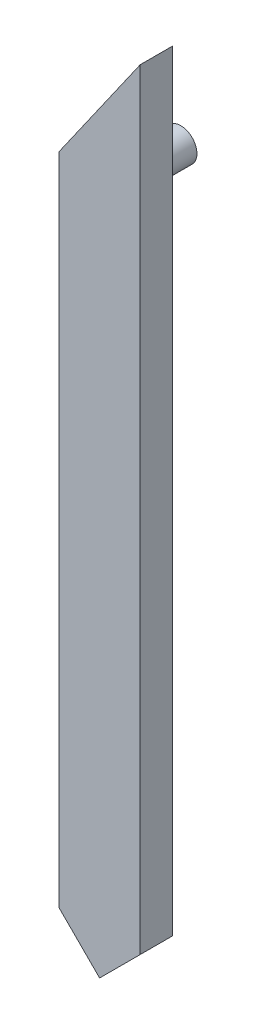
SolidWorks part; units mm, degrees
ref_plane "Front Plane" through (0, 0, 0) normal (0, 0, 1) x (1, 0, 0)
ref_plane "Top Plane" through (0, 0, 0) normal (0, 1, 0) x (1, 0, 0)
ref_plane "Right Plane" through (0, 0, 0) normal (1, 0, 0) x (0, 0, -1)
sketch "Sketch1" plane through (0, 0, 0) normal (0, 0, 1) x (1, 0, 0)
  line L1 (-5, 50) -> (5, 50)
  line L2 (-5, 50) -> (-5, -50)
  line L3 (-5, -50) -> (5, -50)
  line L4 (5, 50) -> (5, -50)
  line L5 (-5, 50) -> (5, -50) construction
  line L6 (-5, -50) -> (5, 50) construction
  point P0 (0, 0)
  dimension "D1" = 100
  dimension "D2" = 10
extrude "Boss-Extrude1" add sketch "Sketch1" along normal blind 4
sketch "Sketch2" plane through (0, 0, 4) normal (0, 0, 1) x (1, 0, 0)
  line L0 (5, 50) -> (-5, 35.7185)
  line L1 (-5, 50) -> (-5, -50) construction
  line L2 (-5, 35.7185) -> (-5, 50)
  line L3 (-5, 50) -> (5, 50)
  dimension "D1" = 145
extrude "Cut-Extrude1" cut sketch "Sketch2" against normal blind 4
chamfer "Chamfer1" distance 5 angle 45 2 edges at (-5, -50, 2) (5, -50, 2)
sketch "Sketch3" plane through (0, 0, 4) normal (0, 0, 1) x (1, 0, 0)
  line L0 (5, -45) -> (5, 50) construction
  circle A0 centre (0, 34) radius 2
  point P6 (5, 50)
  dimension "D1" = 4
  dimension "D2" = 5
  dimension "D3" = 16
extrude "Boss-Extrude2" add sketch "Sketch3" against normal blind 10
